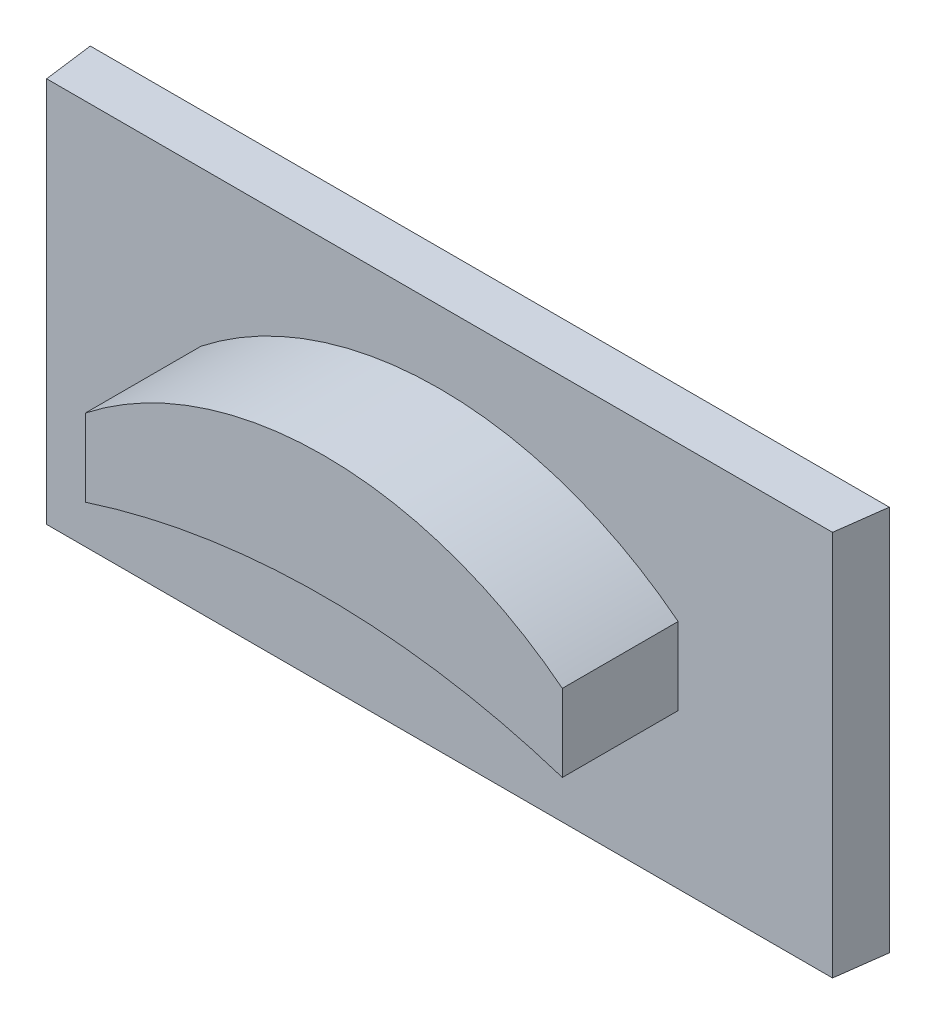
SolidWorks part; units mm, degrees
ref_plane "Plano frontal" through (0, 0, 0) normal (0, 0, 1) x (1, 0, 0)
ref_plane "Plano superior" through (0, 0, 0) normal (0, 1, 0) x (1, 0, 0)
ref_plane "Plano direito" through (0, 0, 0) normal (1, 0, 0) x (0, 0, -1)
sketch "Esboço1" plane through (0, 0, 0) normal (0, 1, 0) x (1, 0, 0)
  line L34 (10.1627, 85.0999) -> (10.3338, 86.3999)
  line L35 (-10.1945, 85.0959) -> (10.1627, 85.0999)
  line L36 (-10.3656, 86.3959) -> (10.3338, 86.3999)
  line L37 (-10.1947, 86.3959) -> (10.1624, 86.3999) construction
  line L38 (-10.3656, 86.3959) -> (-10.1945, 85.0959)
  point P41 (-10.4026, 86.6772)
  point P44 (10.3704, 86.6772)
  dimension "D1" = 20.6994
  dimension "D2" = 20.3571
  dimension "D3" = 1.3
extrude "Ressalto-extrusão1" add sketch "Esboço1" along normal blind 10
sketch "Esboço2" plane through (-0.0167, 0, -85.0979) normal (0.0002, 0, 1) x (1, 0, -0.0002)
  line L0 (-6.1778, 6) -> (-6.1778, 4)
  line L1 (6.1794, 4) -> (6.1794, 6)
  line L4 (-10.1778, 0) -> (10.1794, 0)
  line L5 (10.1794, 0) -> (10.1794, 10)
  line L6 (10.1794, 10) -> (-10.1778, 10)
  line L7 (-10.1778, 10) -> (-10.1778, 0)
  line L8 (-10.1778, 0) -> (10.1794, 0)
  line L9 (10.1794, 0) -> (10.1794, 10)
  line L10 (10.1794, 10) -> (-10.1778, 10)
  line L11 (-10.1778, 10) -> (-10.1778, 0)
  line L13 (-6.1778, 10) -> (-6.1778, 0) construction
  line L16 (6.1794, 0) -> (6.1794, 10) construction
  arc A0 (-6.1778, 4) -> (6.1794, 4) centre (0.0008, -15.0217) cw
  arc A1 (-6.1778, 6) -> (6.1794, 6) centre (0.0008, -1.8629) cw
  point P8 (10.1794, 6)
  point P9 (-10.1778, 6)
  point P10 (-10.1778, 4)
  point P11 (10.1794, 4)
  dimension "D5" = 20
  dimension "D9" = 10
  dimension "D6" = 4
  dimension "D7" = 4
  dimension "D4" = 4
  dimension "D8" = 4
  dimension "D1" = 0
  dimension "D2" = 4
  dimension "D3" = 4
extrude "Ressalto-extrusão2" add sketch "Esboço2" along normal blind 3 contours L0 A0 L1 A1
